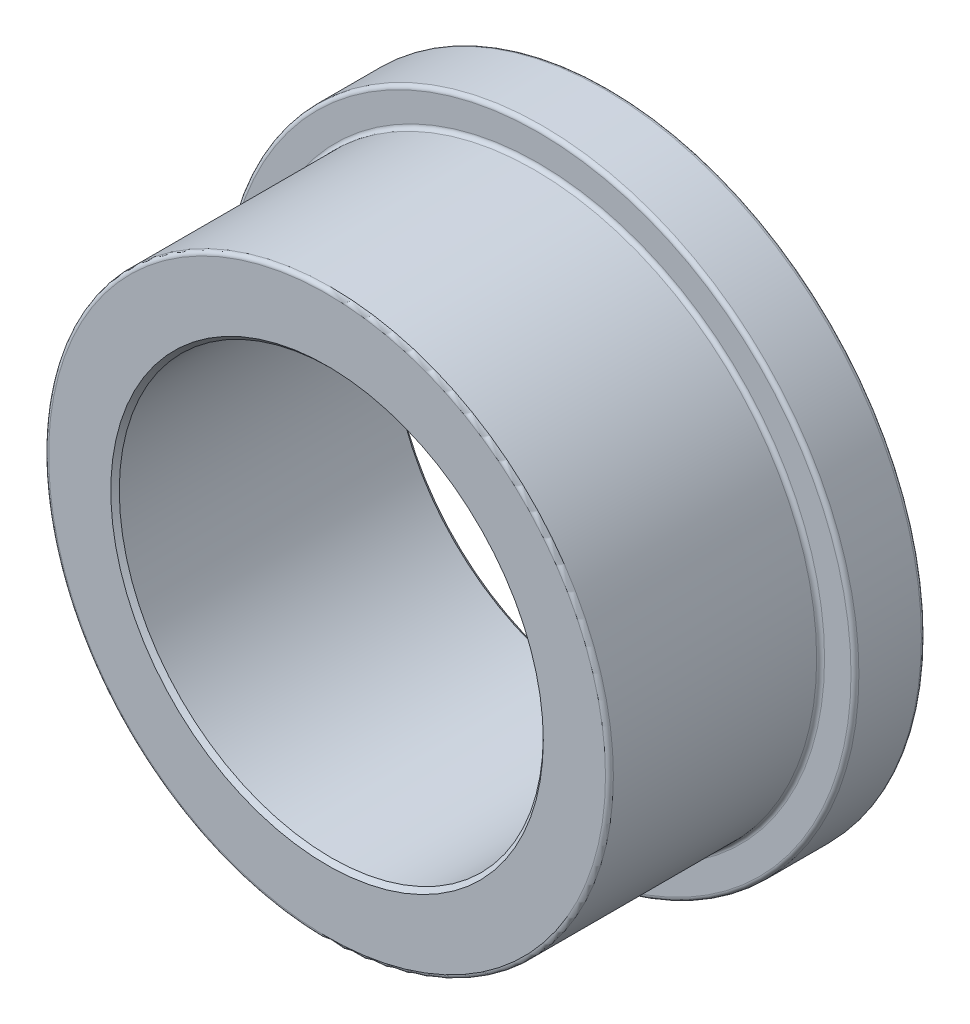
SolidWorks part; units mm, degrees
material "Manganese Bronze"
ref_plane "Front" through (0, 0, 0) normal (0, 0, 1) x (1, 0, 0)
ref_plane "Top" through (0, 0, 0) normal (0, 1, 0) x (1, 0, 0)
ref_plane "Right" through (0, 0, 0) normal (1, 0, 0) x (0, 0, -1)
sketch "Sketch1" plane through (0, 0, 0) normal (0, 0, 1) x (1, 0, 0)
  circle A0 centre (0, 0) radius 9.5631
  circle A1 centre (0, 0) radius 12.7381
  circle A2 centre (0, 0) radius 14.2875
  point P5 (0, 14.2875)
  point P6 (0, 12.7381)
  dimension "ID" = 19.1262
  dimension "OD" = 25.4762
  dimension "FlangeOD" = 28.575
sketch "Sketch2" plane through (0, 0, 0) normal (1, 0, 0) x (0, 0, -1)
  line L0 (0, 0) -> (-12.7, 0)
  point P3 (-3.175, 0)
  point P4 (-12.7, 12.7381)
  dimension "Length" = 12.7
  dimension "FlangeThk" = 3.175
sketch "Sketch3" plane through (0, 0, 0) normal (0, 0, 1) x (1, 0, 0)
  circle A0 centre (0, 0) radius 9.5631 construction
  circle A1 centre (0, 0) radius 12.7381 construction
  circle A2 centre (0, 0) radius 9.5631
  circle A3 centre (0, 0) radius 12.7381
extrude "Boss-Extrude1" add sketch "Sketch3" along normal up to vertex (12.7 mm away) up to point (0, 0, 12.7)
sketch "Sketch4" plane through (0, 0, 0) normal (0, 0, 1) x (1, 0, 0)
  circle A0 centre (0, 0) radius 14.2875 construction
  circle A1 centre (0, 0) radius 12.7381 construction
  circle A2 centre (0, 0) radius 14.2875
  circle A3 centre (0, 0) radius 12.7381
extrude "Boss-Extrude2" add sketch "Sketch4" along normal up to vertex (3.175 mm away) up to point (0, 0, 3.175)
chamfer "Chamfer1" distance 0.1913 angle 45 2 edges at (9.5631, 0, 0) (9.5631, 0, 12.7)
fillet "Fillet1" radius 0.1783 4 edges at (14.2875, 0, 0) (14.2875, 0, 3.175) (12.7381, 0, 3.175) (12.7381, 0, 12.7)
ref_axis "Center Axis 1" through (0, 0, 12.5217) along (0, 0, -1)
equation "\"D1@Chamfer1\"=\"ID@Sketch1\"*.01"
equation "\"D1@Fillet1\"=\"OD@Sketch1\"*.007"
